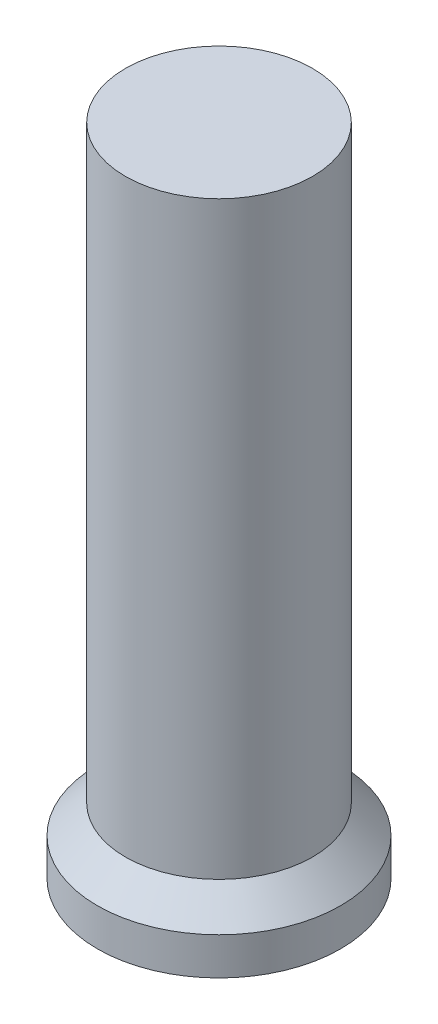
SolidWorks part; units mm, degrees
ref_plane "Спереди" through (0, 0, 0) normal (0, 0, 1) x (1, 0, 0)
ref_plane "Сверху" through (0, 0, 0) normal (0, 1, 0) x (1, 0, 0)
ref_plane "Справа" through (0, 0, 0) normal (1, 0, 0) x (0, 0, -1)
sketch "Эскиз1" plane through (0, 0, 0) normal (0, 1, 0) x (1, 0, 0)
  circle A0 centre (0, 0) radius 6.5
  dimension "D1" = 13
extrude "Бобышка-Вытянуть1" add sketch "Эскиз1" along normal blind 35
sketch "Эскиз2" plane through (0, 35, 0) normal (0, 1, 0) x (1, 0, 0)
  circle A0 centre (0, 0) radius 5
  circle A1 centre (0, 0) radius 6.5
  dimension "D1" = 10
extrude "Вырез-Вытянуть1" cut sketch "Эскиз2" against normal blind 30
chamfer "Фаска1" distance 3 angle 45 1 edges at (0, 5, 6.5)
